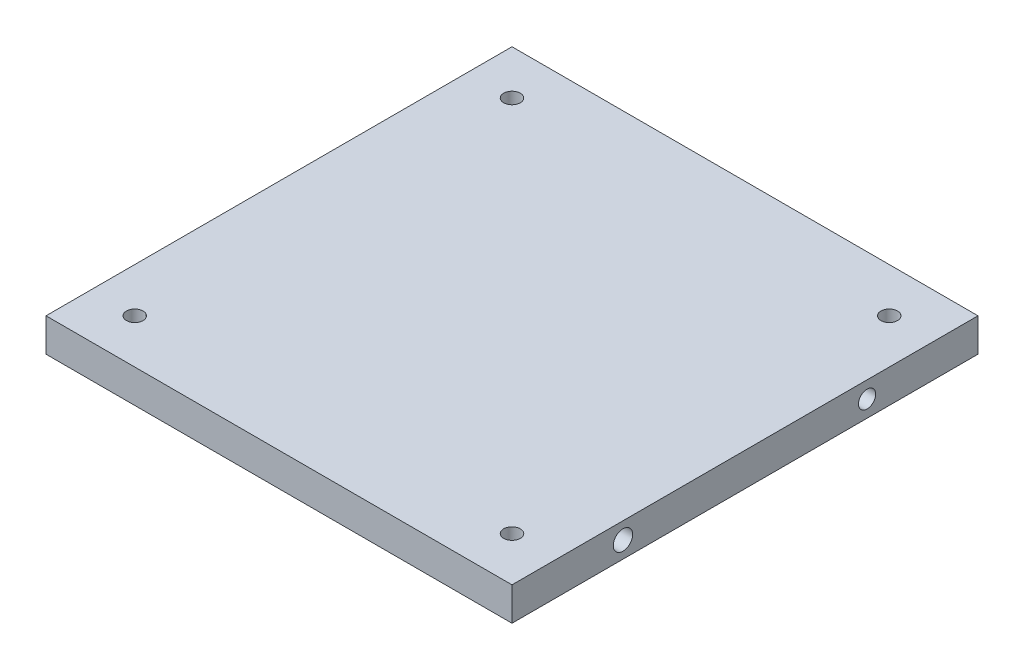
SolidWorks part; units mm, degrees
ref_plane "Front Plane" through (0, 0, 0) normal (0, 0, 1) x (1, 0, 0)
ref_plane "Top Plane" through (0, 0, 0) normal (0, 1, 0) x (1, 0, 0)
ref_plane "Right Plane" through (0, 0, 0) normal (1, 0, 0) x (0, 0, -1)
sketch "Sketch1" plane through (0, 0, 0) normal (0, 1, 0) x (1, 0, 0)
  line L1 (0, 0) -> (84, 0)
  line L2 (0, 0) -> (0, 84)
  line L3 (0, 84) -> (84, 84)
  line L4 (84, 0) -> (84, 84)
  dimension "D1" = 84
  dimension "D2" = 84
extrude "Boss-Extrude1" add sketch "Sketch1" along normal blind 6
sketch "Sketch2" plane through (0, 6, 0) normal (0, 1, 0) x (1, 0, 0)
  line L0 (84, 84) -> (0, 84) construction
  line L1 (0, 84) -> (0, 0) construction
  circle A0 centre (8, 76) radius 1.5
  dimension "D1" = 3
  dimension "D3" = 8
  dimension "D2" = 8
extrude "Cut-Extrude1" cut sketch "Sketch2" against normal blind 6
pattern_linear "LPattern1" count 2 spacing 68 along (1, 0, 0) count 2 spacing 68 along (0, 0, 1) of "Cut-Extrude1"
sketch "Sketch3" plane through (0, 0, 0) normal (-1, 0, 0) x (0, 0, 1)
  line L0 (-84, 3) -> (-20, 3) construction
  line L1 (-84, 6) -> (-84, 0) construction
  line L2 (0, 6) -> (0, 0) construction
  circle A0 centre (-64, 3) radius 1.5499
  circle A1 centre (-20, 3) radius 1.7482
  point P5 (-65.3414, 3)
  point P8 (-74.3438, 3)
  point P9 (-51.074, 3.1685)
  point P10 (-17.6926, 3)
  dimension "D1" = 20
  dimension "D2" = 20
extrude "Cut-Extrude2" cut sketch "Sketch3" against normal blind 10
ref_plane "Plane1" through (42, 0, 0) normal (-1, 0, 0) x (0, 0, 1)
mirror "Mirror1" about plane through (42, 0, 0) normal (-1, 0, 0) of "Cut-Extrude2"
